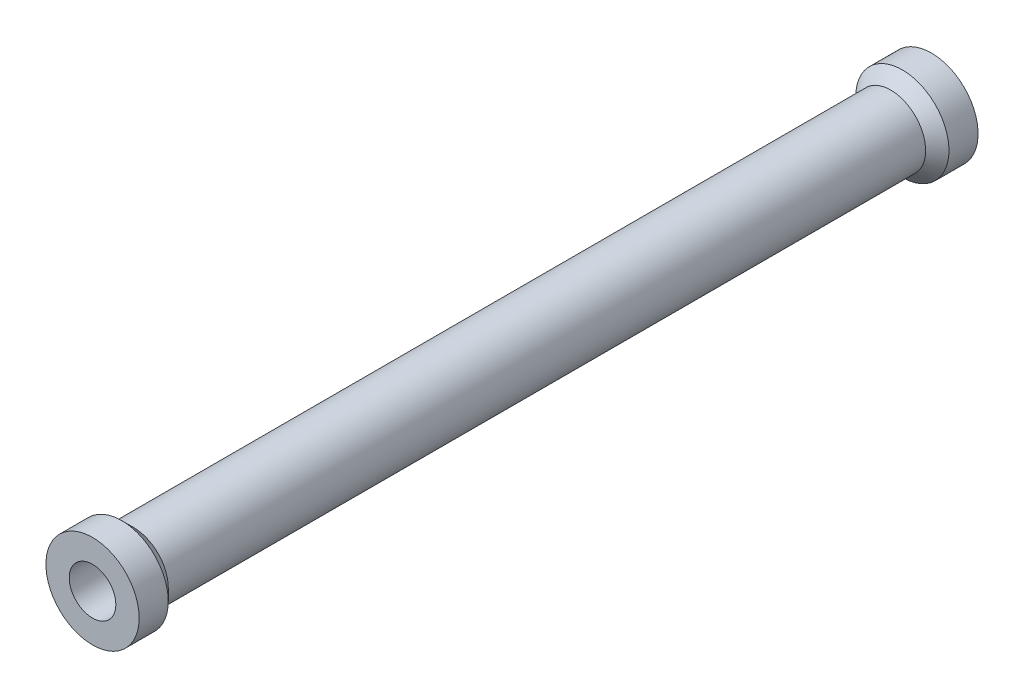
SolidWorks part; units mm, degrees
ref_plane "Front Plane" through (0, 0, 0) normal (0, 0, 1) x (1, 0, 0)
ref_plane "Top Plane" through (0, 0, 0) normal (0, 1, 0) x (1, 0, 0)
ref_plane "Right Plane" through (0, 0, 0) normal (1, 0, 0) x (0, 0, -1)
sketch "Sketch1" plane through (0, 0, 0) normal (0, 0, 1) x (1, 0, 0)
  circle A0 centre (0, 0) radius 4.7625
  dimension "D1" = 9.525
extrude "Boss-Extrude1" add sketch "Sketch1" along normal blind 47.625
sketch "Sketch2" plane through (0, 0, 47.625) normal (0, 0, 1) x (1, 0, 0)
  circle A0 centre (0, 0) radius 6.35
extrude "Boss-Extrude2" add sketch "Sketch2" along normal blind 6.35
chamfer "Chamfer1" distance 2.38 angle 45 1 edges at (6.35, 0, 47.625)
sketch "Sketch3" plane through (0, 0, 53.975) normal (0, 0, 1) x (1, 0, 0)
  circle A0 centre (0, 0) radius 3.175
extrude "Cut-Extrude1" cut sketch "Sketch3" against normal blind 12.7
sketch "Sketch4" plane through (0, 0, 0) normal (0, 0, -1) x (-1, 0, 0)
  circle A0 centre (0, 0) radius 4.7625
extrude "Boss-Extrude3" add sketch "Sketch4" along normal blind 53.975
sketch "Sketch5" plane through (0, 0, -53.975) normal (0, 0, -1) x (-1, 0, 0)
  circle A0 centre (0, 0) radius 6.35
extrude "Boss-Extrude4" add sketch "Sketch5" along normal blind 6.35
chamfer "Chamfer2" distance 2.38 angle 45 1 edges at (-6.35, 0, -53.975)
sketch "Sketch6" plane through (0, 0, -60.325) normal (0, 0, -1) x (-1, 0, 0)
  circle A0 centre (0, 0) radius 3.175
extrude "Cut-Extrude2" cut sketch "Sketch6" against normal blind 12.7
sketch "Sketch7" plane through (0, 0, -60.325) normal (0, 0, -1) x (-1, 0, 0)
  point P0 (0, 0)
